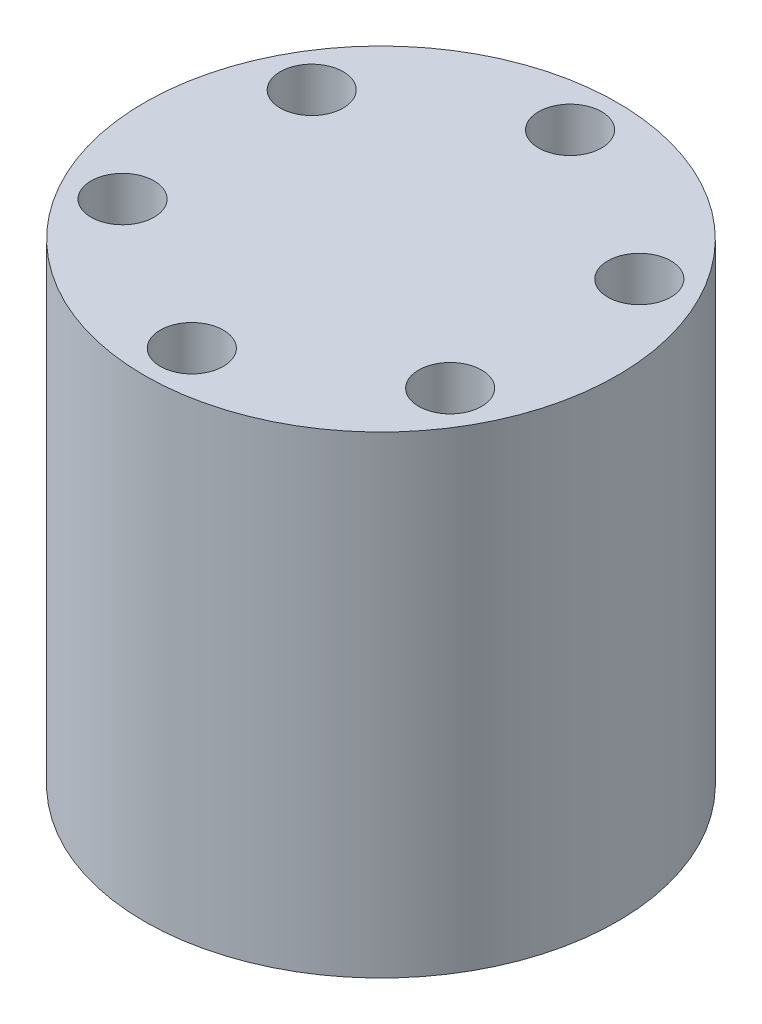
SolidWorks part; units mm, degrees
material "1060 Alloy"
ref_plane "Front Plane" through (0, 0, 0) normal (0, 0, 1) x (1, 0, 0)
ref_plane "Top Plane" through (0, 0, 0) normal (0, 1, 0) x (1, 0, 0)
ref_plane "Right Plane" through (0, 0, 0) normal (1, 0, 0) x (0, 0, -1)
sketch "Sketch1" plane through (0, 0, 0) normal (0, 1, 0) x (1, 0, 0)
  circle A0 centre (0, 0) radius 15
extrude "Boss-Extrude1" add sketch "Sketch1" along normal blind 30
sketch "Sketch2" plane through (0, 0, 0) normal (0, -1, 0) x (1, 0, 0)
  circle A0 centre (0, 0) radius 7
extrude "Boss-Extrude2" add sketch "Sketch2" along normal blind 4
hole_wizard "Ø4.0mm Dowel Hole1" positions "Sketch3" profile "Sketch5" hole size "Ø4.0" standard "ISO" end condition through all
sketch "Sketch3" plane through (0, 0, 0) normal (0, -1, 0) x (-1, 0, 0)
  line L0 (0, 44.7868) -> (0, -44.7868) construction
  point P0 (0, -12)
  dimension "D1" = 12
sketch "Sketch5" plane through (0, 0, 12) normal (1, 0, 0) x (0, 0, -1)
  line L0 (0, 0) -> (0, 30)
  line L1 (0, 30) -> (2, 30)
  line L2 (2, 30) -> (2, 0)
  line L5 (2, 0) -> (0, 0)
  line L11 (0, -6.35) -> (0, 107.95) construction
  dimension "Thru Hole Dia." = 4
  dimension "Thru Hole Depth" = 30
pattern_circular "CirPattern1" count 6 over 360 about axis through (0, 30, 0) along (0, -1, 0) of "Ø4.0mm Dowel Hole1" reverse direction yes
ref_axis "Axis1" through (0, 49.499, 0) along (0, -1, 0)
